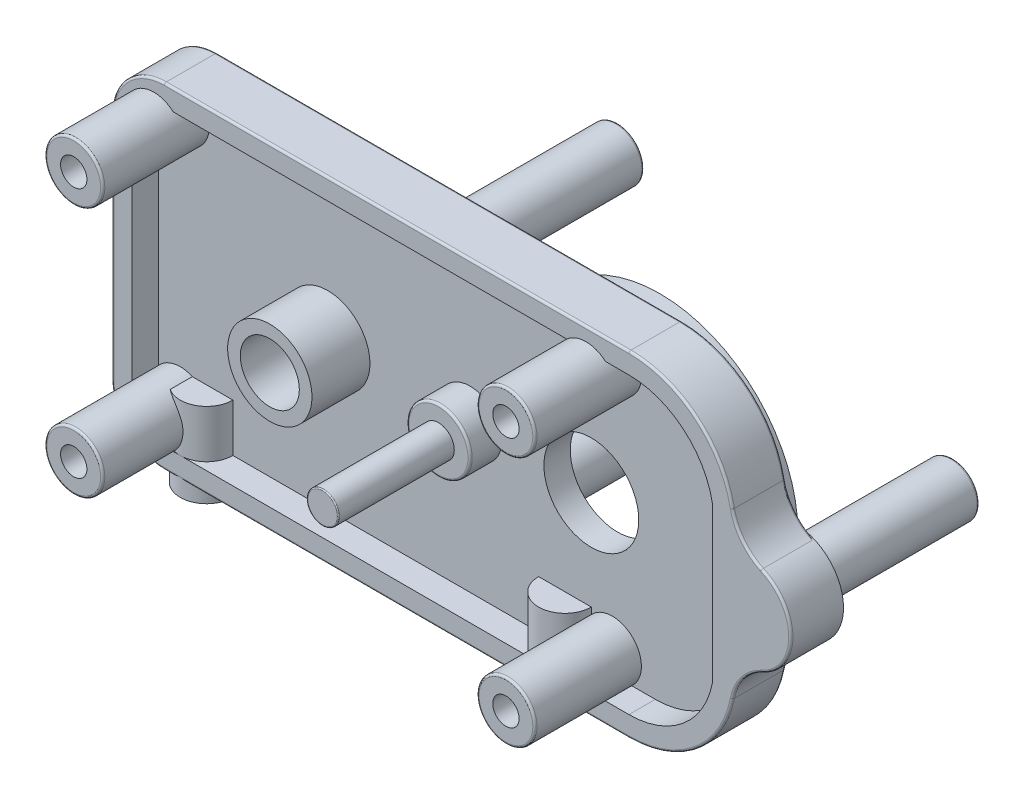
SolidWorks part; units mm, degrees
note: The reader was unsure of these and kept them because the rebuilt part matched: shared geometry of "草图23<3>".
ref_plane "前视基准面" through (0, 0, 0) normal (0, 0, 1) x (1, 0, 0)
ref_plane "上视基准面" through (0, 0, 0) normal (0, 1, 0) x (1, 0, 0)
ref_plane "右视基准面" through (0, 0, 0) normal (1, 0, 0) x (0, 0, -1)
sketch "草图1" plane through (0, 0, 0) normal (0, 0, 1) x (1, 0, 0)
  line L0 (0, 16) -> (50, 16) construction
  line L1 (0, 0.1) -> (50, 0.1)
  line L2 (0, 0.1) -> (0, 31.9)
  line L3 (0, 31.9) -> (50, 31.9)
  line L4 (50, 0.1) -> (59.0704, 0.1)
  line L5 (50, 31.9) -> (59.0704, 31.9)
  line L6 (59.0704, 31.9) -> (59.0704, 20.2477)
  line L7 (59.0704, 20.2477) -> (61.6342, 20.2477)
  line L8 (59.0704, 11.7523) -> (61.6342, 11.7523)
  line L9 (59.0704, 0.1) -> (59.0704, 11.7523)
  line L10 (45, 27.9) -> (45, -2.3835) construction
  circle A0 centre (4, 27.9) radius 1.5 construction
  circle A1 centre (45, 27.9) radius 1.5 construction
  circle A2 centre (45, 4.1) radius 1.5 construction
  circle A3 centre (4, 4.1) radius 1.5 construction
  circle A4 centre (18, 16.1) radius 2.8
  circle A5 centre (43, 16) radius 4.5
  arc A7 (61.6342, 11.7523) -> (61.6342, 20.2477) centre (59.8, 16) ccw
  arc A8 (58.895, 20.3918) -> (60.5407, 19.7498) centre (60.5678, 22.2496) ccw construction
  circle A14 centre (59.8, 16) radius 1.6 construction
  point P22 (38.5, 16)
  dimension "D3" = 3
  dimension "D10" = 18
  dimension "D11" = 5.6
  dimension "D14" = 9
  dimension "D8" = 43
  dimension "D1" = 50
  dimension "D2" = 31.8
  dimension "D6" = 4
  dimension "D7" = 4
  dimension "D9" = 4
  dimension "D12" = 4
  dimension "D13" = 41
  dimension "D15" = 16.8
  dimension "D4" = 2
  dimension "D5" = 2
extrude "凸台-拉伸1" add sketch "草图1" along normal blind 5
sketch "草图3" plane through (0, 0, 0) normal (0, 0, -1) x (-1, 0, 0)
  circle A0 centre (-43, 16) radius 11.1
  circle A1 centre (-43, 16) radius 13.1
  dimension "D1" = 22.2
  dimension "D2" = 2
extrude "凸台-拉伸2" add sketch "草图3" along normal blind 4
fillet "圆角1" radius 10 2 edges at (59.0704, 0.1, 2.5) (59.0704, 31.9, 2.5)
fillet "圆角2" radius 5 2 edges at (59.0704, 11.7523, 2.5) (59.0704, 20.2477, 2.5)
fillet "圆角3" radius 5 2 edges at (0, 0.1, 2.5) (0, 31.9, 2.5)
sketch "草图4" plane through (0, 0, 5) normal (0, 0, 1) x (1, 0, 0)
  line L3 (56.9731, 23.4329) -> (56.9731, 8.5671)
  line L6 (1.95, 26.9) -> (1.95, 5.1)
  line L7 (5, 2.05) -> (49.0704, 2.05)
  line L8 (49.0704, 29.95) -> (5, 29.95)
  line L9 (1.95, 26.9) -> (1.95, 5.1)
  line L10 (5, 2.05) -> (49.0704, 2.05)
  line L11 (49.0704, 29.95) -> (5, 29.95)
  arc A14 (1.95, 5.1) -> (5, 2.05) centre (5, 5.1) ccw
  arc A15 (49.0704, 2.05) -> (56.9731, 8.5671) centre (49.0704, 10.1) ccw
  arc A16 (60.9881, 13.6013) -> (56.9731, 8.5671) centre (63.7959, 7.2437) ccw
  arc A17 (60.9881, 13.6013) -> (60.9881, 18.3987) centre (59.8, 16) ccw
  arc A18 (56.9731, 23.4329) -> (60.9881, 18.3987) centre (63.7959, 24.7563) ccw
  arc A19 (56.9731, 23.4329) -> (49.0704, 29.95) centre (49.0704, 21.9) ccw
  arc A20 (5, 29.95) -> (1.95, 26.9) centre (5, 26.9) ccw
  arc A21 (1.95, 5.1) -> (5, 2.05) centre (5, 5.1) ccw
  arc A22 (49.0704, 2.05) -> (56.9731, 8.5671) centre (49.0704, 10.1) ccw
  arc A26 (56.9731, 23.4329) -> (49.0704, 29.95) centre (49.0704, 21.9) ccw
  arc A27 (5, 29.95) -> (1.95, 26.9) centre (5, 26.9) ccw
  dimension "D1" = 1.95
extrude "切除-拉伸1" cut sketch "草图4" against normal blind 2.5
sketch "草图5" plane through (0, 0, 2.5) normal (0, 0, 1) x (1, 0, 0)
  circle A0 centre (45, 27.9) radius 1.5 construction
  circle A1 centre (45, 4.1) radius 1.5 construction
  circle A2 centre (4, 4.1) radius 1.5 construction
  circle A3 centre (4, 27.9) radius 1.5 construction
  circle A8 centre (45, 4.1) radius 1.5 construction
  circle A9 centre (45, 27.9) radius 1.5 construction
  circle A10 centre (4, 27.9) radius 1.5 construction
  circle A11 centre (4, 4.1) radius 1.5 construction
  circle A12 centre (45, 4.1) radius 2.75
  circle A13 centre (45, 27.9) radius 2.75
  circle A14 centre (4, 27.9) radius 2.75
  circle A15 centre (4, 4.1) radius 2.75
  dimension "D1" = 1.25
extrude "凸台-拉伸3" add sketch "草图5" along normal blind 10.1
sketch "草图6" plane through (0, 0, 2.5) normal (0, 0, 1) x (1, 0, 0)
  circle A0 centre (18, 16.1) radius 2.8 construction
  circle A1 centre (18, 16.1) radius 2.8
  circle A2 centre (18, 16.1) radius 4
  dimension "D1" = 1.2
extrude "凸台-拉伸4" add sketch "草图6" along normal blind 5.5
sketch "草图7" plane through (0, 0, 2.5) normal (0, 0, 1) x (1, 0, 0)
  line L0 (0, 16) -> (50, 16) construction
  line L1 (31.5, 16) -> (18, 16.1) construction
  circle A0 centre (31.5, 16) radius 3
  circle A1 centre (31.5, 16) radius 1.5
  dimension "D1" = 6
  dimension "D3" = 13.5
  dimension "D2" = 1.5
extrude "凸台-拉伸5" add sketch "草图7" along normal blind 3
hole_wizard "M3 螺纹孔1" positions "草图9" profile "草图8" tap size "M3" standard "Gb"
sketch "草图9" plane through (0, 0, 12.6) normal (0, 0, 1) x (1, 0, 0)
  point P0 (4, 27.9)
  point P3 (4, 4.1)
  point P6 (45, 4.1)
  point P9 (45, 27.9)
sketch "草图8" plane through (4, 27.9, 12.6) normal (1, 0, 0) x (0, -1, 0)
  line L0 (0, 0) -> (0, 7.2511)
  line L1 (0, 7.2511) -> (1.25, 6.5)
  line L2 (1.25, 6.5) -> (1.25, 0)
  line L5 (1.25, 0) -> (0, 0)
  line L10 (0, 7.2511) -> (-1.25, 6.5) construction
  line L11 (0, -6.35) -> (0, 107.95) construction
  dimension "螺纹孔钻头直径" = 2.5
  dimension "螺纹孔钻头深度" = 6.5
  dimension "导头角度" = 118
cosmetic thread "孔螺蚊线1" parameters "D1"=4, "D2"=3
cosmetic thread "孔螺蚊线2" parameters "D1"=4, "D2"=3
cosmetic thread "孔螺蚊线3" parameters "D1"=4, "D2"=3
cosmetic thread "孔螺蚊线4" parameters "D1"=4, "D2"=3
ref_plane "基准面1" through (0, -1.4, 0) normal (0, -1, 0) x (-1, 0, 0)
sketch "草图10" plane through (0, -1.4, 0) normal (0, -1, 0) x (-1, 0, 0)
  line L0 (-5, -5) -> (-49.0704, -5) construction
  circle A0 centre (-6.5, -2.5) radius 2.5
  circle A1 centre (-40.5, -2.5) radius 2.5
  circle A2 centre (-40.5, -2.5) radius 1.25 construction
  circle A3 centre (-6.5, -2.5) radius 1.25 construction
  dimension "D1" = 5
  dimension "D2" = 5
  dimension "D3" = 6.5
  dimension "D4" = 34
  dimension "D5" = 1.25
  dimension "D6" = 1.25
sketch "草图12" plane through (0, 0, 0) normal (0, 0, -1) x (-1, 0, 0)
  line L0 (-7.0896, 16) -> (-52.5795, 16) construction
  line L1 (-52.5795, 16) -> (-67.1558, 16) construction
  line L2 (-43, 11.5) -> (-43, 20.5) construction
  circle A0 centre (-59.8, 16) radius 2.5
  circle A1 centre (-27.9966, 27.65) radius 2.5
  circle A2 centre (-27.9966, 4.35) radius 2.5
  circle A3 centre (-43, 16) radius 4.5 construction
  dimension "D1" = 5
  dimension "D2" = 5
  dimension "D3" = 5
  dimension "D4" = 23.3
  dimension "D5" = 33.87
extrude "凸台-拉伸7" add sketch "草图12" along normal blind 15
fillet "圆角4" radius 0.5 3 edges at (30.4966, 27.65, 0) (30.4966, 4.35, 0) (62.3, 16, 0)
hole_wizard "M3 螺纹孔2" positions "草图14" profile "草图13" tap size "M3" standard "Gb"
sketch "草图14" plane through (0, 0, -15) normal (0, 0, -1) x (-1, 0, 0)
  point P0 (-59.8, 16)
  point P3 (-27.9966, 27.65)
  point P6 (-27.9966, 4.35)
sketch "草图13" plane through (59.8, 16, -15) normal (1, 0, 0) x (0, 1, 0)
  line L0 (0, 0) -> (0, 7.2511)
  line L1 (0, 7.2511) -> (1.25, 6.5)
  line L2 (1.25, 6.5) -> (1.25, 0)
  line L5 (1.25, 0) -> (0, 0)
  line L10 (0, 7.2511) -> (-1.25, 6.5) construction
  line L11 (0, -6.35) -> (0, 107.95) construction
  dimension "螺纹孔钻头直径" = 2.5
  dimension "螺纹孔钻头深度" = 6.5
  dimension "导头角度" = 118
cosmetic thread "孔螺蚊线5" parameters "D1"=4, "D2"=3
cosmetic thread "孔螺蚊线6" parameters "D1"=4, "D2"=3
cosmetic thread "孔螺蚊线7" parameters "D1"=4, "D2"=3
fillet "圆角5" radius 0.2 3 edges at (25.4966, 4.35, -15) (25.4966, 27.65, -15) (57.3, 16, -15)
fillet "圆角6" radius 0.2 4 edges at (6.75, 27.9, 12.6) (47.75, 27.9, 12.6) (47.75, 4.1, 12.6) (6.75, 4.1, 12.6)
fillet "圆角7" radius 0.2 1 edges at (34.5, 16, 5.5)
fillet "圆角9" radius 0.2 10 edges at (27.0352, 0.1, 5) (1.4645, 1.5645, 5) (0, 16, 5) (1.4645, 30.4355, 5) (27.0352, 31.9, 5) (55.4327, 29.615, 5) (59.8388, 21.7, 5) (64.4268, 16, 5) (59.8388, 10.3, 5) (55.4327, 2.385, 5)
fillet "圆角10" radius 0.2 9 edges at (27.0352, 31.9, 0) (1.4645, 30.4355, 0) (0, 16, 0) (1.4645, 1.5645, 0) (27.0352, 0.1, 0) (55.4327, 2.385, 0) (59.8388, 10.3, 0) (59.8388, 21.7, 0) (55.4327, 29.615, 0)
ref_plane "基准面2" through (0, 33.4, 0) normal (0, 1, 0) x (1, 0, 0)
sketch "草图16" plane through (0, 33.4, 0) normal (0, 1, 0) x (1, 0, 0)
  line L0 (0, -2.5) -> (12.2538, -2.5) construction
  line L1 (0, -4.8) -> (0, -0.2) construction
  line L2 (34, -2.5) -> (46.2538, -2.5) construction
  circle A0 centre (6.5, -2.5) radius 2.5
  circle A1 centre (6.5, -2.5) radius 1 construction
  circle A2 centre (40.5, -2.5) radius 2.5
  circle A3 centre (40.5, -2.5) radius 1 construction
  dimension "D1" = 5
  dimension "D2" = 6.5
  dimension "D3" = 1.5
  dimension "D4" = 2
extrude "凸台-拉伸8" [suppressed] add sketch "草图16" against normal blind 8
sketch "草图17" [suppressed] plane through (0, 33.4, 0) normal (0, 1, 0) x (1, 0, 0)
  circle A0 centre (6.5, -2.5) radius 1 construction
  circle A1 centre (40.5, -2.5) radius 1 construction
  circle A2 centre (6.5, -2.5) radius 1
  circle A3 centre (40.5, -2.5) radius 1
extrude "切除-拉伸3" [suppressed] cut sketch "草图17" against normal blind 5
sketch "草图23" plane through (0, -1.4, 0) normal (0, -1, 0) x (-1, 0, 0)
  line L0 (0, -0.2) -> (0, -4.8) construction
  line L1 (0, -0.2) -> (0, -4.8) construction
  line L2 (0, -2.5) -> (-15.9312, -2.5) construction
  line L4 (-23.5, 1.6992) -> (-23.5, -8.5684) construction
  circle A0 centre (-6.5, -2.5) radius 2.5
  circle A1 centre (-6.5, -2.5) radius 1
  circle A2 centre (-40.5, -2.5) radius 1
  circle A3 centre (-40.5, -2.5) radius 2.5
  dimension "D1" = 5
  dimension "D2" = 1.5
  dimension "D3" = 6.5
  dimension "D4" = 17
extrude "凸台-拉伸9" add sketch "草图23" against normal blind 8 contours A0 A1 | A1 | A2 | A3 A2
extrude "切除-拉伸4" cut sketch "草图23<3>" against normal blind 5 contours A1 | A2
sketch "草图23<3>" plane through (0, -1.4, 0) normal (0, -1, 0) x (-1, 0, 0) same geometry as "草图23"
hole_wizard "M3 螺纹孔6" positions "3D草图6" profile "草图25" tap size "M3" standard "GB"
sketch3d "3D草图6"
  line L0 (6.5, 3.6, 2.5) -> (6.5, -1.4, 2.5) construction
  line L1 (40.5, 3.6, 2.5) -> (40.5, -1.4, 2.5) construction
  point P17 (6.5, -1.4, 2.5)
  point P19 (40.5, -1.4, 2.5)
sketch "草图25" plane through (6.5, -1.4, 2.5) normal (1, 0, 0) x (0, 0, -1)
  line L0 (0, 0) -> (0, 6.2511)
  line L1 (0, 6.2511) -> (1.25, 5.5)
  line L2 (1.25, 5.5) -> (1.25, 0)
  line L5 (1.25, 0) -> (0, 0)
  line L10 (0, 6.2511) -> (-1.25, 5.5) construction
  line L11 (0, -6.35) -> (0, 107.95) construction
  dimension "螺纹孔钻头直径" = 2.5
  dimension "螺纹孔钻头深度" = 5.5
  dimension "导头角度" = 118
cosmetic thread "孔螺蚊线20" parameters "D1"=4, "D2"=3
cosmetic thread "孔螺蚊线21" parameters "D1"=4, "D2"=3
sketch "草图26" plane through (0, 0, 2.5) normal (0, 0, 1) x (1, 0, 0)
  circle A1 centre (31.5, 16) radius 1.5
  circle A2 centre (31.5, 16) radius 1.5
  dimension "D1" = 0
extrude "凸台-拉伸10" add sketch "草图26" along normal blind 14
fillet "圆角11" radius 0.1 1 edges at (33, 16, 16.5)
